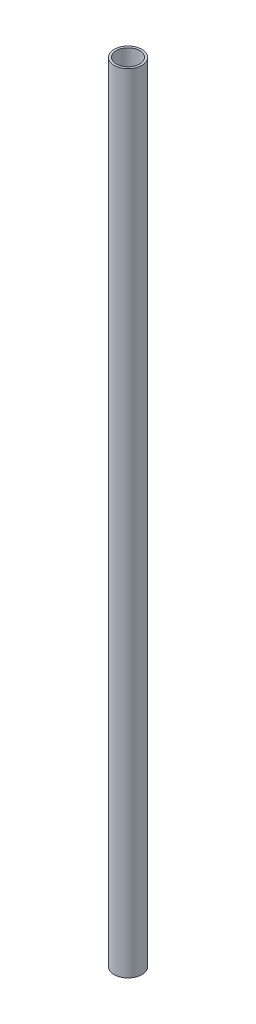
SolidWorks part; units mm, degrees
material "AISI 4130 Steel, annealed at 865C"
ref_plane "Front Plane" through (0, 0, 0) normal (0, 0, 1) x (1, 0, 0)
ref_plane "Top Plane" through (0, 0, 0) normal (0, 1, 0) x (1, 0, 0)
ref_plane "Right Plane" through (0, 0, 0) normal (1, 0, 0) x (0, 0, -1)
sketch "Sketch1" plane through (0, 0, 0) normal (0, 1, 0) x (1, 0, 0)
  circle A0 centre (0, 0) radius 6.6929
  circle A1 centre (0, 0) radius 7.9375
  dimension "D1" = 15.875
  dimension "D2" = 13.3858
extrude "Boss-Extrude1" add sketch "Sketch1" along normal blind 450.85
ref_axis "Axis1" through (0, 450.85, 0) along (0, -1, 0)
